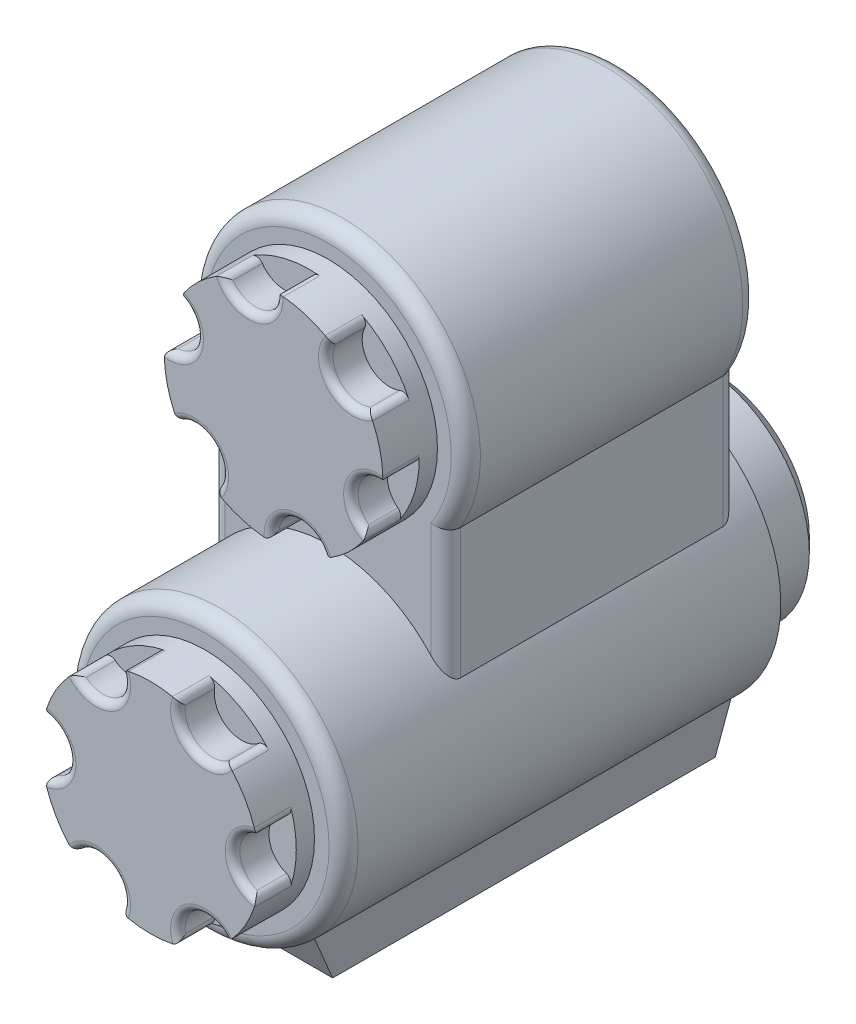
SolidWorks part; units mm, degrees
material "PET"
ref_plane "Front Plane" through (0, 0, 0) normal (0, 0, 1) x (1, 0, 0)
ref_plane "Top Plane" through (0, 0, 0) normal (0, 1, 0) x (1, 0, 0)
ref_plane "Right Plane" through (0, 0, 0) normal (1, 0, 0) x (0, 0, -1)
sketch "Sketch2" plane through (0, 0, 0) normal (0, 0, 1) x (1, 0, 0)
  circle A2 centre (325.6373, 52.475) radius 18.9484
  circle A3 centre (325.6373, 52.475) radius 18.9484
  dimension "D1" = 1.27
extrude "Boss-Extrude1" add sketch "Sketch2" against normal blind 12.7
sketch "Sketch3" plane through (0, 0, 0) normal (0, 0, 1) x (1, 0, 0)
  circle A0 centre (325.6373, 52.475) radius 24.13 construction
  circle A1 centre (325.6373, 52.475) radius 24.13
extrude "Boss-Extrude2" add sketch "Sketch3" along normal blind 76.2
sketch "Sketch4" plane through (0, 0, 76.2) normal (0, 0, 1) x (1, 0, 0)
  circle A0 centre (325.6373, 52.475) radius 19.05
  dimension "D1" = 38.1
extrude "Boss-Extrude3" add sketch "Sketch4" along normal blind 9.525
sketch "Sketch5" plane through (0, 0, 85.725) normal (0, 0, 1) x (1, 0, 0)
  line L0 (325.6373, 52.475) -> (344.6873, 52.475) construction
  circle A0 centre (325.6373, 52.475) radius 19.05 construction
  circle A1 centre (344.6873, 52.475) radius 4.7625
  dimension "D1" = 9.525
extrude "Cut-Extrude1" cut sketch "Sketch5" against normal blind 6.35
fillet "Fillet1" radius 1.27 3 edges at (344.092, 57.2001, 82.55) (339.9248, 52.475, 85.725) (344.092, 47.7499, 82.55)
pattern_circular "CirPattern1" count 6 over 360 about axis through (325.6373, 52.475, 85.725) along (0, 0, -1) of "Cut-Extrude1", "Fillet1" reverse direction yes
chamfer "Chamfer1" distance 2.54 angle 45 1 edges at (344.5857, 52.475, -12.7)
sketch "Sketch6" plane through (-0.0014, 0, 3.7009) normal (0.0004, 0, -1) x (-1, 0, -0.0004)
  circle A0 centre (-325.5233, 100.6049) radius 24
  ellipse E0 centre (-325.6373, 52.475) end of major axis (-325.6373, 76.605) minor radius 24.13 construction
  dimension "D1" = 48.1299
extrude "Boss-Extrude4" add sketch "Sketch6" against normal blind 50.8 separate body
sketch "Sketch7" plane through (-0.0014, 0, 3.7009) normal (0.0004, 0, -1) x (-1, 0, -0.0004)
  line L0 (-346.0236, 87.995) -> (-346.0236, 64.955) construction
  line L1 (-305.0236, 65.3846) -> (-346.0236, 65.3846)
  line L2 (-305.0236, 65.3846) -> (-305.0236, 88.1244)
  line L4 (-346.0236, 65.3846) -> (-346.0236, 88.1254)
  line L5 (-305.0236, 64.955) -> (-305.0236, 87.995) construction
  circle A0 centre (-325.5233, 100.6049) radius 24 construction
  arc A1 (-346.0236, 88.1254) -> (-305.0236, 88.1244) centre (-325.5233, 100.6049) ccw
  ellipse E1 centre (-325.6373, 52.475) end of major axis (-325.6373, 76.605) minor radius 24.13 construction
  circle M6 centre (-325.5233, 100.6049) radius 24
extrude "Boss-Extrude5" add sketch "Sketch7" against normal up to surface (50.8 mm away) contours L4 M6 | L1 L2 A1 region at (325.5223, 73.0425, 3.8219) up to face at (301.503, 100.6049, 54.613)
sketch "Sketch8" plane through (-0.0202, 0, 54.5009) normal (-0.0004, 0, 1) x (1, 0, 0.0004)
  circle A0 centre (325.5233, 100.6049) radius 19.05
  dimension "D1" = 38.1
extrude "Boss-Extrude6" add sketch "Sketch8" along normal blind 9.525
sketch "Sketch9" plane through (-0.0238, 0, 64.0259) normal (-0.0004, 0, 1) x (1, 0, 0.0004)
  line L0 (325.5233, 100.6049) -> (343.7707, 95.1338) construction
  circle A0 centre (325.5233, 100.6049) radius 19.05 construction
  circle A1 centre (343.7707, 95.1338) radius 4.7625
  dimension "D1" = 9.525
extrude "Cut-Extrude2" cut sketch "Sketch9" against normal blind 6.35
fillet "Fillet2" radius 1.27 3 edges at (344.5349, 99.8309, 60.9789) (339.1851, 96.5016, 64.152) (341.8208, 90.7787, 60.9779)
pattern_circular "CirPattern2" count 6 over 360 about axis through (325.4995, 100.6049, 64.1469) along (0.0004, 0, -1) of "Cut-Extrude2", "Fillet2" reverse direction yes
fillet "Fillet3" radius 2.54 7 edges at (349.7673, 52.475, 76.2) (346.0033, 76.771, 54.6295) (325.5024, 124.6049, 54.6219) (305.0033, 76.7545, 54.6143) (346.0222, 76.7561, 3.8295) (325.5213, 124.6049, 3.8219) (305.0222, 76.7545, 3.8143)
ref_axis "Axis1" through (325.6373, 52.475, 73.66) along (0, 0, -1)
ref_plane "Plane1" through (325.6373, 0, 0) normal (1, 0, 0) x (0, 0, -1)
sketch "Sketch10" plane through (0, 0, 0) normal (0, 0, -1) x (-1, 0, 0)
  line L0 (-325.6373, 40.513) -> (-325.6373, -40.513) construction
  line L1 (-312.9373, 23.5825) -> (-338.3373, 23.5825)
  line L2 (-312.9373, 23.5825) -> (-312.9373, 33.1075)
  line L3 (-312.9373, 33.1075) -> (-338.3373, 33.1075)
  line L4 (-338.3373, 23.5825) -> (-338.3373, 33.1075)
  line L5 (-312.9373, 23.5825) -> (-338.3373, 33.1075) construction
  line L6 (-312.9373, 33.1075) -> (-338.3373, 23.5825) construction
  circle A0 centre (-325.6373, 52.475) radius 24.13 construction
  point P0 (-325.6373, 28.345)
  dimension "D1" = 4.7625
  dimension "D2" = 25.4
extrude "Boss-Extrude7" add sketch "Sketch10" against normal offset from surface (66.675 mm away) 9.525 up to face at (347.2273, 52.475, 76.2)
draft "Draft2" type of draft neutral plane draft angle 30 faces to draft 1 face at (325.6373, 26.8669, 66.675) neutral plane through (312.9373, 23.5825, 103.3272) neutral plane normal (0, -1, 0) parameters "D1"=30
draft "Draft3" type of draft neutral plane draft angle 15 faces to draft 1 face at (312.9373, 27.77, 34.5463) neutral plane through (312.9373, 23.5825, 103.3272) neutral plane normal (0, -1, 0) parameters "D1"=15
draft "Draft4" type of draft neutral plane draft angle 15 faces to draft 1 face at (338.3373, 27.77, 34.5463) neutral plane through (312.9373, 23.5825, 103.3272) neutral plane normal (0, -1, 0) parameters "D1"=15
